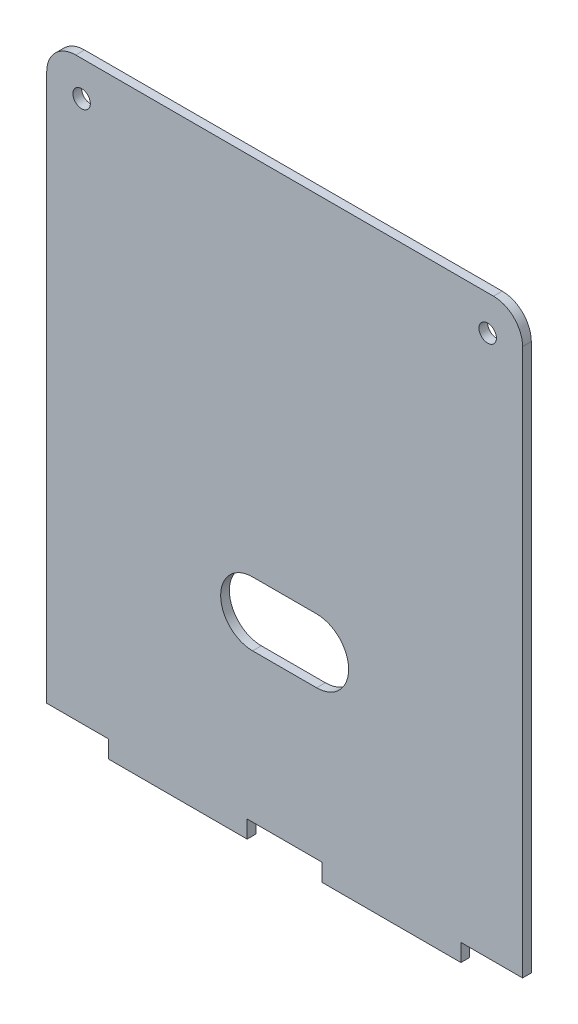
SolidWorks part; units mm, degrees
ref_plane "Front Plane" through (0, 0, 0) normal (0, 0, 1) x (1, 0, 0)
ref_plane "Top Plane" through (0, 0, 0) normal (0, 1, 0) x (1, 0, 0)
ref_plane "Right Plane" through (0, 0, 0) normal (1, 0, 0) x (0, 0, -1)
sketch "Sketch1" plane through (0, 0, 0) normal (0, 0, 1) x (1, 0, 0)
  line L1 (0, 0) -> (81.8, 0)
  line L2 (0, 0) -> (0, 102)
  line L3 (0, 102) -> (81.8, 102)
  line L4 (81.8, 0) -> (81.8, 102)
  dimension "D1" = 81.8
  dimension "D2" = 102
extrude "Boss-Extrude1" add sketch "Sketch1" along normal blind 1.5
sketch "Sketch2" plane through (0, 0, 1.5) normal (0, 0, 1) x (1, 0, 0)
  line L0 (40.9, 102) -> (40.9, 0)
  line L1 (81.8, 102) -> (0, 102) construction
  line L2 (0, 0) -> (81.8, 0) construction
  line L3 (81.8, 0) -> (81.8, 3)
  line L4 (0, 0) -> (10.6, 0)
  line L5 (0, 0) -> (0, 3)
  line L6 (0, 3) -> (10.6, 3)
  line L7 (10.6, 0) -> (10.6, 3)
  line L8 (34.455, 0) -> (47.345, 0)
  line L9 (34.455, 0) -> (34.455, 3)
  line L10 (34.455, 3) -> (47.345, 3)
  line L11 (47.345, 0) -> (47.345, 3)
  line L12 (81.8, 0) -> (71.2, 0)
  line L13 (71.2, 0) -> (71.2, 3)
  line L14 (81.8, 3) -> (71.2, 3)
  line L15 (0, 102) -> (0, 0) construction
  circle A0 centre (6, 96) radius 1.5
  circle A1 centre (75.8, 96) radius 1.5
  line M8 (0, 102) -> (0, 0)
  line M9 (0, 0) -> (81.8, 0)
  line M10 (81.8, 0) -> (81.8, 102)
  dimension "D5" = 6
  dimension "D1" = 3
  dimension "D2" = 10.6
  dimension "D3" = 12.89
  dimension "D4" = 6.445
  dimension "D6" = 6
extrude "Cut-Extrude1" cut sketch "Sketch2" against normal through all contours L7 L6 M9 M8 | L11 L10 L0 M9 | L10 L9 L0 M9 | L14 L13 M10 M9 | A0 | A1 region at (44.1225, 1.5, 1.5) region at (37.6775, 1.5, 1.5) region at (76.5, 1.5, 1.5) region at (5.3, 1.5, 1.5)
sketch "Sketch3" plane through (0, 0, 1.5) normal (0, 0, 1) x (1, 0, 0)
  line L0 (0, 34) -> (81.8, 34)
  line L1 (0, 102) -> (0, 3) construction
  line L2 (81.8, 3) -> (81.8, 102) construction
  line L3 (40.9, 102) -> (40.9, 3)
  line L4 (81.8, 102) -> (0, 102) construction
  line L5 (34.455, 3) -> (47.345, 3) construction
  line L6 (35.4, 39.5) -> (46.4, 39.5)
  line L7 (35.4, 28.5) -> (46.4, 28.5)
  circle A0 centre (35.4, 34) radius 5.5
  circle A1 centre (46.4, 34) radius 5.5
  point P19 (40.9, 28.5)
  point P20 (40.9, 39.5)
  dimension "D1" = 5.5
  dimension "D2" = 11
  dimension "D3" = 68
extrude "Cut-Extrude2" cut sketch "Sketch3" against normal through all contours L0 A0 | L0 A0 | A1 L0 | A1 L0 | A0 L7 L3 | L7 A1 L3 | L3 A1 L6 | A0 L3 L6 region at (46.4, 36.3343, 1.5) region at (35.4, 31.6657, 1.5) region at (39.6715, 38.2715, 1.5) region at (42.1285, 29.7285, 1.5) region at (35.4, 36.3343, 1.5) region at (39.6715, 29.7285, 1.5) region at (42.1285, 38.2715, 1.5) region at (46.4, 31.6657, 1.5)
fillet "Fillet1" radius 5 2 edges at (0, 102, 0.75) (81.8, 102, 0.75)
